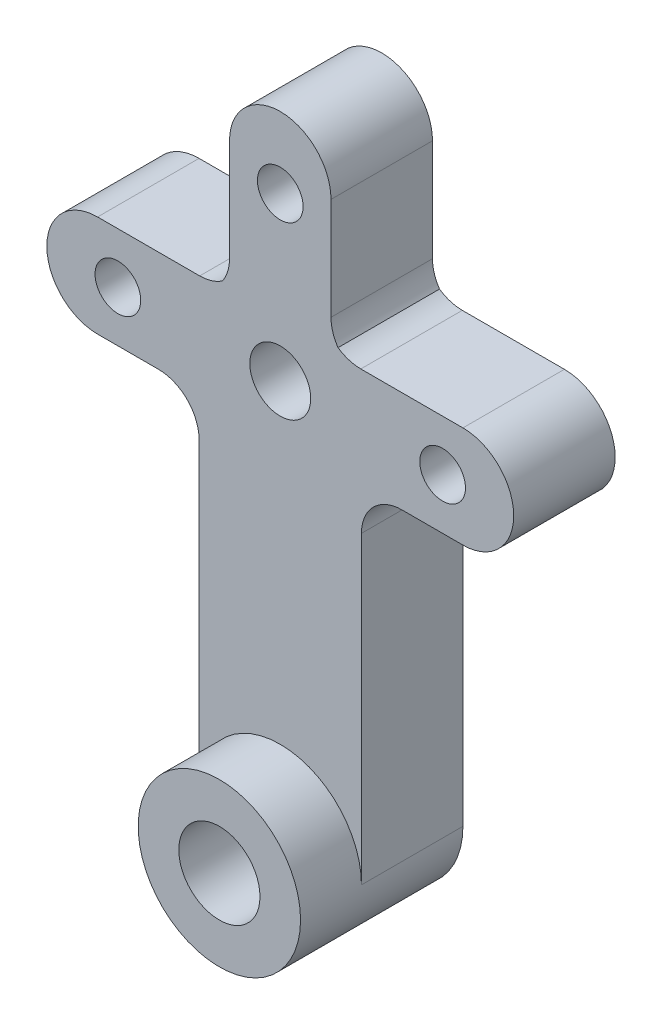
SolidWorks part; units mm, degrees
ref_plane "Plan de face" through (0, 0, 0) normal (0, 0, 1) x (1, 0, 0)
ref_plane "Plan de dessus" through (0, 0, 0) normal (0, 1, 0) x (1, 0, 0)
ref_plane "Plan de droite" through (0, 0, 0) normal (1, 0, 0) x (0, 0, -1)
sketch "Esquisse1" plane through (0, 0, 0) normal (0, 0, 1) x (1, 0, 0)
  circle A0 centre (0, 0) radius 26.25
  dimension "D1" = 52.5
extrude "Boss.-Extru.1" add sketch "Esquisse1" along normal blind 5
sketch "Esquisse2" plane through (0, 0, 5) normal (0, 0, 1) x (1, 0, 0)
  circle A0 centre (0, 0) radius 1.5
  dimension "D1" = 3
extrude "Enlèv. mat.-Extru.1" cut sketch "Esquisse2" against normal up to surface (5 mm away) up to face at (26.25, 0, 0)
sketch "Esquisse3" plane through (0, 0, 5) normal (0, 0, 1) x (1, 0, 0)
  line L0 (0, -19.5) -> (0, -17.5) construction
  line L3 (0, 0) -> (0, -19.5) construction
  line L6 (4, 0) -> (4, -19.5)
  line L9 (-4, 0) -> (-4, -19.5)
  line L12 (0, 0) -> (9, 0) construction
  line L13 (0, 2.5) -> (9, 2.5)
  line L14 (0, -2.5) -> (9, -2.5)
  line L18 (0, 0) -> (-9, 0) construction
  line L19 (0, -2.5) -> (-9, -2.5)
  line L20 (0, 2.5) -> (-9, 2.5)
  line L21 (0, 0) -> (0, 9) construction
  line L22 (-2.5, 0) -> (-2.5, 9)
  line L23 (2.5, 0) -> (2.5, 9)
  line L57 (0, 0) -> (0, -9) construction
  line L58 (2.5, 0) -> (2.5, -9)
  line L59 (-2.5, 0) -> (-2.5, -9)
  line L60 (0, 0) -> (0, -9) construction
  line L61 (2.5, 0) -> (2.5, -9)
  line L62 (-2.5, 0) -> (-2.5, -9)
  circle A0 centre (0, -19.5) radius 2
  circle A1 centre (0, 0) radius 1.5 construction
  arc A2 (4, 0) -> (-4, 0) centre (0, 0) ccw
  arc A3 (-4, -19.5) -> (4, -19.5) centre (0, -19.5) ccw
  arc A4 (0, 2.5) -> (0, -2.5) centre (0, 0) ccw
  arc A5 (9, -2.5) -> (9, 2.5) centre (9, 0) ccw
  arc A8 (0, -2.5) -> (0, 2.5) centre (0, 0) ccw
  arc A9 (-9, 2.5) -> (-9, -2.5) centre (-9, 0) ccw
  arc A10 (-2.5, 0) -> (2.5, 0) centre (0, 0) ccw
  arc A11 (2.5, 9) -> (-2.5, 9) centre (0, 9) ccw
  circle A15 centre (0, 0) radius 26.25
  circle A16 centre (0, 0) radius 26.25
  arc A39 (2.5, 0) -> (-2.5, 0) centre (0, 0) ccw
  arc A40 (-2.5, -9) -> (2.5, -9) centre (0, -9) ccw
  point P2 (0, -6.5)
  point P6 (0, -9.75)
  point P11 (0, 7.6855)
  point P15 (4.5, 0)
  point P18 (-8.3537, 0)
  point P23 (0.001, -5.499)
  point P26 (6.9416, 0)
  point P34 (-4.5, 0)
  point P42 (0, 4.5)
  point P47 (0, 0)
  point P54 (0.001, -5.499)
  point P61 (0.001, -5.499)
  point P68 (0.001, -5.499)
  point P75 (0.001, -5.499)
  point P82 (0.001, -5.499)
  point P89 (0.001, -5.499)
  point P96 (0.001, -5.499)
  point P103 (0, -4.5)
  point P110 (0, -4.5)
  point P117 (0, -4.5)
  point P124 (0, -4.5)
  point P131 (0, -4.5)
  circle M3 centre (0, 0) radius 26.25
  dimension "D1" = 4
  dimension "D2" = 19.5
  dimension "D3" = 2
  dimension "D4" = 5
  dimension "D5" = 9
  dimension "D7" = 0
  dimension "D6" = 4
extrude "Enlèv. mat.-Extru.2" cut sketch "Esquisse3" against normal up to surface (5 mm away) contours A11 L23 A2 L13 A5 L14 L6 A3 L9 L19 A9 L20 L22 M3 | A0 region at (0, -19.5, 5) region at (-25.5075, 0, 5) up to face at (1.5, 0, 0)
fillet "Congé1" radius 2 6 edges at (-4, -2.5, 2.5) (-3.1225, 2.5, 2.5) (-2.5, 3.1225, 2.5) (3.1225, 2.5, 2.5) (2.5, 3.1225, 2.5) (4, -2.5, 2.5)
sketch "Esquisse4" plane through (0, 0, 5) normal (0, 0, 1) x (1, 0, 0)
  line L0 (-8, 0) -> (8, 0)
  circle A1 centre (-8, 0) radius 1.125
  circle A2 centre (8, 0) radius 1.125
  circle A3 centre (0, -8) radius 1.125
  circle A4 centre (-8, 0) radius 1.125
  circle A5 centre (0, 8) radius 1.125
  point P6 (0, 0)
  point P17 (0, 0)
  dimension "D2" = 2.25
  dimension "D3" = 2.25
  dimension "D1" = 16
  dimension "D5" = 8
  dimension "D4" = 4
extrude "Enlèv. mat.-Extru.3" cut sketch "Esquisse4" against normal blind 10 contours A1 | A5 | A2 region at (8, 1.0932, 5) region at (-9.0932, 0, 5) region at (0, 8, 5)
sketch "Esquisse5" plane through (0, 0, 5) normal (0, 0, 1) x (1, 0, 0)
  circle A0 centre (0, -19.5) radius 2
  circle A1 centre (0, -19.5) radius 4
  arc A2 (-4, -19.5) -> (4, -19.5) centre (0, -19.5) ccw construction
  circle A3 centre (0, -19.5) radius 2 construction
extrude "Boss.-Extru.2" add sketch "Esquisse5" along normal blind 3
